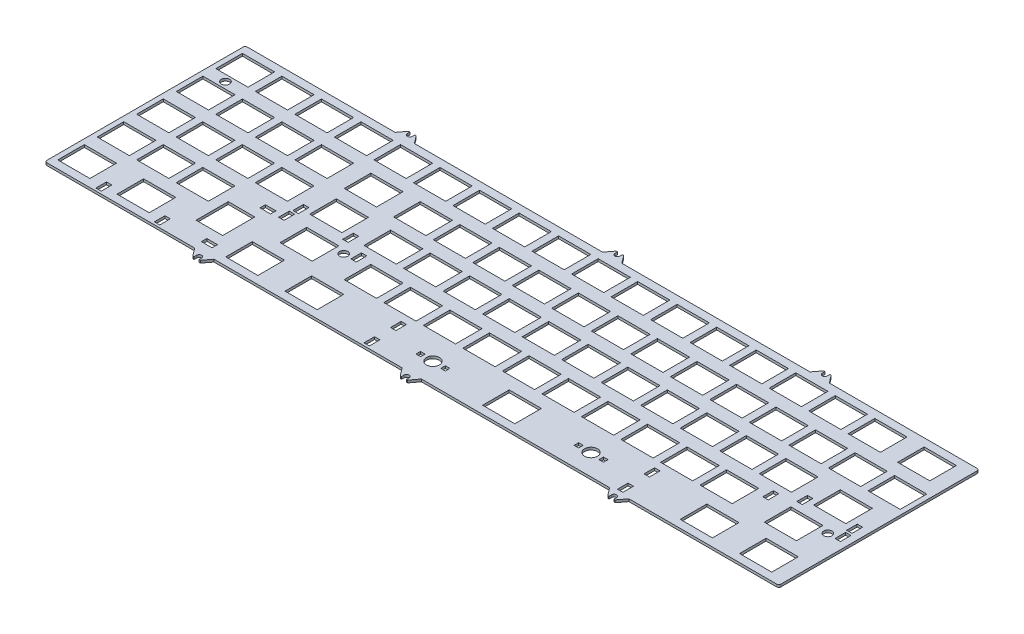
SolidWorks part; units mm, degrees
ref_plane "Front Plane" through (0, 0, 0) normal (0, 0, 1) x (1, 0, 0)
ref_plane "Top Plane" through (0, 0, 0) normal (0, 1, 0) x (1, 0, 0)
ref_plane "Right Plane" through (0, 0, 0) normal (1, 0, 0) x (0, 0, -1)
sketch "Sketch2" plane through (0, 0, 0) normal (0, 1, 0) x (1, 0, 0)
  line L0 (137.0625, 39.4) -> (121.4625, 39.4)
  line L1 (121.4625, 39.4) -> (121.4625, 26.6)
  line L2 (121.4625, 26.6) -> (137.0625, 26.6)
  line L3 (137.0625, 26.6) -> (137.0625, 39.4)
  line L4 (127.5375, 58.45) -> (111.9375, 58.45)
  line L5 (111.9375, 58.45) -> (111.9375, 45.65)
  line L6 (111.9375, 45.65) -> (127.5375, 45.65)
  line L7 (127.5375, 45.65) -> (127.5375, 58.45)
  line L8 (122.775, 77.5) -> (107.175, 77.5)
  line L9 (107.175, 77.5) -> (107.175, 64.7)
  line L10 (107.175, 64.7) -> (122.775, 64.7)
  line L11 (122.775, 64.7) -> (122.775, 77.5)
  line L12 (325.7312, 43.1) -> (325.7312, 48.2)
  line L13 (325.7312, 48.2) -> (323.1312, 48.2)
  line L14 (323.1312, 48.2) -> (323.1312, 43.1)
  line L15 (323.1312, 43.1) -> (325.7312, 43.1)
  line L16 (347.1312, 43.1) -> (347.1312, 48.2)
  line L17 (347.1312, 48.2) -> (349.7312, 48.2)
  line L18 (349.7312, 48.2) -> (349.7312, 43.1)
  line L19 (349.7312, 43.1) -> (347.1312, 43.1)
  line L20 (104.2437, 43.1) -> (104.2437, 48.2)
  line L21 (104.2437, 48.2) -> (106.8437, 48.2)
  line L22 (106.8437, 48.2) -> (106.8437, 43.1)
  line L23 (106.8437, 43.1) -> (104.2437, 43.1)
  line L24 (315.5687, 36.85) -> (315.5687, 41.95)
  line L25 (315.5687, 41.95) -> (312.9687, 41.95)
  line L26 (312.9687, 41.95) -> (312.9687, 36.85)
  line L27 (312.9687, 36.85) -> (315.5687, 36.85)
  line L28 (347.7687, 36.85) -> (347.7687, 41.95)
  line L29 (347.7687, 41.95) -> (350.3687, 41.95)
  line L30 (350.3687, 41.95) -> (350.3687, 36.85)
  line L31 (350.3687, 36.85) -> (347.7687, 36.85)
  line L32 (114.4062, 36.85) -> (114.4062, 41.95)
  line L33 (114.4062, 41.95) -> (117.0062, 41.95)
  line L34 (117.0062, 41.95) -> (117.0062, 36.85)
  line L35 (117.0062, 36.85) -> (114.4062, 36.85)
  line L36 (155.1875, 5) -> (155.1875, 10.1)
  line L37 (155.1875, 10.1) -> (152.5875, 10.1)
  line L38 (152.5875, 10.1) -> (152.5875, 5)
  line L39 (152.5875, 5) -> (155.1875, 5)
  line L40 (183.9625, 15.05) -> (183.9625, 12.85)
  line L41 (183.9625, 12.85) -> (181.7625, 12.85)
  line L42 (181.7625, 12.85) -> (181.7625, 15.05)
  line L43 (181.7625, 15.05) -> (183.9625, 15.05)
  line L44 (169.8125, 12.85) -> (169.8125, 15.05)
  line L45 (169.8125, 15.05) -> (172.0125, 15.05)
  line L46 (172.0125, 15.05) -> (172.0125, 12.85)
  line L47 (172.0125, 12.85) -> (169.8125, 12.85)
  line L48 (246.0125, 15.05) -> (246.0125, 12.85)
  line L49 (246.0125, 12.85) -> (248.2125, 12.85)
  line L50 (248.2125, 12.85) -> (248.2125, 15.05)
  line L51 (248.2125, 15.05) -> (246.0125, 15.05)
  line L52 (260.1625, 12.85) -> (260.1625, 15.05)
  line L53 (260.1625, 15.05) -> (257.9625, 15.05)
  line L54 (257.9625, 15.05) -> (257.9625, 12.85)
  line L55 (257.9625, 12.85) -> (260.1625, 12.85)
  line L56 (82.8437, 43.1) -> (82.8437, 48.2)
  line L57 (82.8437, 48.2) -> (80.2437, 48.2)
  line L58 (80.2437, 48.2) -> (80.2437, 43.1)
  line L59 (80.2437, 43.1) -> (82.8437, 43.1)
  line L60 (82.2062, 36.85) -> (82.2062, 41.95)
  line L61 (82.2062, 41.95) -> (79.6062, 41.95)
  line L62 (79.6062, 41.95) -> (79.6062, 36.85)
  line L63 (79.6062, 36.85) -> (82.2062, 36.85)
  line L64 (25.975, 5) -> (25.975, 10.1)
  line L65 (25.975, 10.1) -> (23.375, 10.1)
  line L66 (23.375, 10.1) -> (23.375, 5)
  line L67 (23.375, 5) -> (25.975, 5)
  line L68 (51.575, 5) -> (51.575, 10.1)
  line L69 (51.575, 10.1) -> (54.175, 10.1)
  line L70 (54.175, 10.1) -> (54.175, 5)
  line L71 (54.175, 5) -> (51.575, 5)
  line L72 (76.3, 10.675) -> (71.2, 10.675)
  line L73 (71.2, 10.675) -> (71.2, 8.075)
  line L74 (71.2, 8.075) -> (76.3, 8.075)
  line L75 (76.3, 8.075) -> (76.3, 10.675)
  line L76 (76.3, 36.275) -> (71.2, 36.275)
  line L77 (71.2, 36.275) -> (71.2, 38.875)
  line L78 (71.2, 38.875) -> (76.3, 38.875)
  line L79 (76.3, 38.875) -> (76.3, 36.275)
  line L80 (155.1875, 22.9) -> (155.1875, 17.8)
  line L81 (155.1875, 17.8) -> (152.5875, 17.8)
  line L82 (152.5875, 17.8) -> (152.5875, 22.9)
  line L83 (152.5875, 22.9) -> (155.1875, 22.9)
  line L84 (277.3875, 22.9) -> (277.3875, 17.8)
  line L85 (277.3875, 17.8) -> (274.7875, 17.8)
  line L86 (274.7875, 17.8) -> (274.7875, 22.9)
  line L87 (274.7875, 22.9) -> (277.3875, 22.9)
  line L88 (274.7875, 5) -> (274.7875, 10.1)
  line L89 (274.7875, 10.1) -> (277.3875, 10.1)
  line L90 (277.3875, 10.1) -> (277.3875, 5)
  line L91 (277.3875, 5) -> (274.7875, 5)
  line L92 (0, 4.75) -> (0, 99.35)
  line L93 (353.775, 4.75) -> (353.775, 99.35)
  line L94 (75.0875, 104.1) -> (72.2375, 100.35)
  line L95 (75.0875, 104.1) -> (75.6875, 104.1)
  line L96 (75.6875, 104.1) -> (75.6875, 103.6)
  line L97 (78.6875, 104.1) -> (81.5375, 100.35)
  line L98 (78.6875, 104.1) -> (78.0875, 104.1)
  line L99 (78.0875, 104.1) -> (78.0875, 103.6)
  line L100 (175.0875, 104.1) -> (172.2375, 100.35)
  line L101 (175.0875, 104.1) -> (175.6875, 104.1)
  line L102 (178.6875, 104.1) -> (181.5375, 100.35)
  line L103 (178.6875, 104.1) -> (178.0875, 104.1)
  line L104 (275.0875, 104.1) -> (272.2375, 100.35)
  line L105 (275.0875, 104.1) -> (275.6875, 104.1)
  line L106 (278.6875, 104.1) -> (281.5375, 100.35)
  line L107 (278.6875, 104.1) -> (278.0875, 104.1)
  line L108 (272.2375, 100.35) -> (181.5375, 100.35)
  line L109 (172.2375, 100.35) -> (81.5375, 100.35)
  line L110 (72.2375, 100.35) -> (1, 100.35)
  line L111 (352.775, 100.35) -> (281.5375, 100.35)
  line L112 (272.2375, 3.75) -> (181.5375, 3.75)
  line L113 (172.2375, 3.75) -> (81.5375, 3.75)
  line L114 (72.2375, 3.75) -> (1, 3.75)
  line L115 (352.775, 3.75) -> (281.5375, 3.75)
  line L116 (331.0625, 83.75) -> (346.5625, 83.75)
  line L117 (346.5625, 83.75) -> (346.5625, 96.55)
  line L118 (346.5625, 96.55) -> (331.0625, 96.55)
  line L119 (331.0625, 96.55) -> (331.0625, 83.75)
  line L120 (307.25, 83.75) -> (322.75, 83.75)
  line L121 (322.75, 83.75) -> (322.75, 96.55)
  line L122 (322.75, 96.55) -> (307.25, 96.55)
  line L123 (307.25, 96.55) -> (307.25, 83.75)
  line L124 (288.2, 83.75) -> (303.7, 83.75)
  line L125 (303.7, 83.75) -> (303.7, 96.55)
  line L126 (303.7, 96.55) -> (288.2, 96.55)
  line L127 (288.2, 96.55) -> (288.2, 83.75)
  line L128 (269.15, 83.75) -> (284.65, 83.75)
  line L129 (284.65, 83.75) -> (284.65, 96.55)
  line L130 (284.65, 96.55) -> (269.15, 96.55)
  line L131 (269.15, 96.55) -> (269.15, 83.75)
  line L132 (250.1, 83.75) -> (265.6, 83.75)
  line L133 (265.6, 83.75) -> (265.6, 96.55)
  line L134 (265.6, 96.55) -> (250.1, 96.55)
  line L135 (250.1, 96.55) -> (250.1, 83.75)
  line L136 (231.05, 83.75) -> (246.55, 83.75)
  line L137 (246.55, 83.75) -> (246.55, 96.55)
  line L138 (246.55, 96.55) -> (231.05, 96.55)
  line L139 (231.05, 96.55) -> (231.05, 83.75)
  line L140 (212, 83.75) -> (227.5, 83.75)
  line L141 (227.5, 83.75) -> (227.5, 96.55)
  line L142 (227.5, 96.55) -> (212, 96.55)
  line L143 (212, 96.55) -> (212, 83.75)
  line L144 (192.95, 83.75) -> (208.45, 83.75)
  line L145 (208.45, 83.75) -> (208.45, 96.55)
  line L146 (208.45, 96.55) -> (192.95, 96.55)
  line L147 (192.95, 96.55) -> (192.95, 83.75)
  line L148 (173.9, 83.75) -> (189.4, 83.75)
  line L149 (189.4, 83.75) -> (189.4, 96.55)
  line L150 (189.4, 96.55) -> (173.9, 96.55)
  line L151 (173.9, 96.55) -> (173.9, 83.75)
  line L152 (154.85, 83.75) -> (170.35, 83.75)
  line L153 (170.35, 83.75) -> (170.35, 96.55)
  line L154 (170.35, 96.55) -> (154.85, 96.55)
  line L155 (154.85, 96.55) -> (154.85, 83.75)
  line L156 (135.8, 83.75) -> (151.3, 83.75)
  line L157 (151.3, 83.75) -> (151.3, 96.55)
  line L158 (151.3, 96.55) -> (135.8, 96.55)
  line L159 (135.8, 96.55) -> (135.8, 83.75)
  line L160 (116.75, 83.75) -> (132.25, 83.75)
  line L161 (132.25, 83.75) -> (132.25, 96.55)
  line L162 (132.25, 96.55) -> (116.75, 96.55)
  line L163 (116.75, 96.55) -> (116.75, 83.75)
  line L164 (97.7, 83.75) -> (113.2, 83.75)
  line L165 (113.2, 83.75) -> (113.2, 96.55)
  line L166 (113.2, 96.55) -> (97.7, 96.55)
  line L167 (97.7, 96.55) -> (97.7, 83.75)
  line L168 (78.65, 83.75) -> (94.15, 83.75)
  line L169 (94.15, 83.75) -> (94.15, 96.55)
  line L170 (94.15, 96.55) -> (78.65, 96.55)
  line L171 (78.65, 96.55) -> (78.65, 83.75)
  line L172 (59.6, 77.5) -> (75.1, 77.5)
  line L173 (75.1, 64.7) -> (75.1, 77.5)
  line L174 (75.1, 96.55) -> (59.6, 96.55)
  line L175 (59.6, 77.5) -> (59.6, 64.7)
  line L176 (40.55, 77.5) -> (56.05, 77.5)
  line L177 (56.05, 64.7) -> (56.05, 77.5)
  line L178 (56.05, 96.55) -> (40.55, 96.55)
  line L179 (40.55, 77.5) -> (40.55, 64.7)
  line L180 (21.5, 77.5) -> (37, 77.5)
  line L181 (37, 64.7) -> (37, 77.5)
  line L182 (37, 96.55) -> (21.5, 96.55)
  line L183 (21.5, 77.5) -> (21.5, 64.7)
  line L184 (2.45, 77.5) -> (17.95, 77.5)
  line L185 (17.95, 64.7) -> (17.95, 77.5)
  line L186 (17.95, 96.55) -> (2.45, 96.55)
  line L187 (2.45, 77.5) -> (2.45, 64.7)
  line L188 (59.6, 64.7) -> (75.1, 64.7)
  line L189 (75.1, 83.75) -> (75.1, 96.55)
  line L190 (75.1, 83.75) -> (59.6, 83.75)
  line L191 (59.6, 96.55) -> (59.6, 83.75)
  line L192 (40.55, 64.7) -> (56.05, 64.7)
  line L193 (56.05, 83.75) -> (56.05, 96.55)
  line L194 (56.05, 83.75) -> (40.55, 83.75)
  line L195 (40.55, 96.55) -> (40.55, 83.75)
  line L196 (21.5, 64.7) -> (37, 64.7)
  line L197 (37, 83.75) -> (37, 96.55)
  line L198 (37, 83.75) -> (21.5, 83.75)
  line L199 (21.5, 96.55) -> (21.5, 83.75)
  line L200 (2.45, 64.7) -> (17.95, 64.7)
  line L201 (17.95, 83.75) -> (17.95, 96.55)
  line L202 (17.95, 83.75) -> (2.45, 83.75)
  line L203 (2.45, 96.55) -> (2.45, 83.75)
  line L204 (59.55, 45.65) -> (75.05, 45.65)
  line L205 (75.05, 45.65) -> (75.05, 58.45)
  line L206 (75.05, 58.45) -> (59.55, 58.45)
  line L207 (59.55, 58.45) -> (59.55, 45.65)
  line L208 (40.5, 45.65) -> (56, 45.65)
  line L209 (56, 45.65) -> (56, 58.45)
  line L210 (56, 58.45) -> (40.5, 58.45)
  line L211 (40.5, 58.45) -> (40.5, 45.65)
  line L212 (21.45, 45.65) -> (36.95, 45.65)
  line L213 (36.95, 45.65) -> (36.95, 58.45)
  line L214 (36.95, 58.45) -> (21.45, 58.45)
  line L215 (21.45, 58.45) -> (21.45, 45.65)
  line L216 (2.4, 45.65) -> (17.9, 45.65)
  line L217 (17.9, 45.65) -> (17.9, 58.45)
  line L218 (17.9, 58.45) -> (2.4, 58.45)
  line L219 (2.4, 58.45) -> (2.4, 45.65)
  line L220 (40.5, 26.6) -> (56, 26.6)
  line L221 (56, 26.6) -> (56, 39.4)
  line L222 (56, 39.4) -> (40.5, 39.4)
  line L223 (40.5, 39.4) -> (40.5, 26.6)
  line L224 (21.45, 26.6) -> (36.95, 26.6)
  line L225 (36.95, 26.6) -> (36.95, 39.4)
  line L226 (36.95, 39.4) -> (21.45, 39.4)
  line L227 (21.45, 39.4) -> (21.45, 26.6)
  line L228 (2.4, 26.6) -> (17.9, 26.6)
  line L229 (17.9, 26.6) -> (17.9, 39.4)
  line L230 (17.9, 39.4) -> (2.4, 39.4)
  line L231 (2.4, 39.4) -> (2.4, 26.6)
  line L232 (2.45, 7.55) -> (17.95, 7.55)
  line L233 (17.95, 7.55) -> (17.95, 20.35)
  line L234 (17.95, 20.35) -> (2.45, 20.35)
  line L235 (2.45, 20.35) -> (2.45, 7.55)
  line L236 (31.025, 7.55) -> (46.525, 7.55)
  line L237 (46.525, 7.55) -> (46.525, 20.35)
  line L238 (46.525, 20.35) -> (31.025, 20.35)
  line L239 (31.025, 20.35) -> (31.025, 7.55)
  line L240 (83.4125, 7.55) -> (98.9125, 7.55)
  line L241 (98.9125, 7.55) -> (98.9125, 20.35)
  line L242 (98.9125, 20.35) -> (83.4125, 20.35)
  line L243 (83.4125, 20.35) -> (83.4125, 7.55)
  line L244 (111.9875, 7.55) -> (127.4875, 7.55)
  line L245 (127.4875, 7.55) -> (127.4875, 20.35)
  line L246 (127.4875, 20.35) -> (111.9875, 20.35)
  line L247 (111.9875, 20.35) -> (111.9875, 7.55)
  line L248 (90.5562, 26.6) -> (106.0562, 26.6)
  line L249 (106.0562, 26.6) -> (106.0562, 39.4)
  line L250 (106.0562, 39.4) -> (90.5562, 39.4)
  line L251 (90.5562, 39.4) -> (90.5562, 26.6)
  line L252 (85.7937, 45.65) -> (101.2937, 45.65)
  line L253 (101.2937, 45.65) -> (101.2937, 58.45)
  line L254 (101.2937, 58.45) -> (85.7937, 58.45)
  line L255 (85.7937, 58.45) -> (85.7937, 45.65)
  line L256 (83.4125, 64.7) -> (98.9125, 64.7)
  line L257 (98.9125, 64.7) -> (98.9125, 77.5)
  line L258 (98.9125, 77.5) -> (83.4125, 77.5)
  line L259 (83.4125, 77.5) -> (83.4125, 64.7)
  line L260 (328.6812, 45.65) -> (344.1812, 45.65)
  line L261 (344.1812, 45.65) -> (344.1812, 58.45)
  line L262 (344.1812, 58.45) -> (328.6812, 58.45)
  line L263 (328.6812, 58.45) -> (328.6812, 45.65)
  line L264 (207.2375, 7.55) -> (222.7375, 7.55)
  line L265 (222.7375, 7.55) -> (222.7375, 20.35)
  line L266 (222.7375, 20.35) -> (207.2375, 20.35)
  line L267 (207.2375, 20.35) -> (207.2375, 7.55)
  line L268 (302.4875, 7.55) -> (317.9875, 7.55)
  line L269 (317.9875, 7.55) -> (317.9875, 20.35)
  line L270 (317.9875, 20.35) -> (302.4875, 20.35)
  line L271 (302.4875, 20.35) -> (302.4875, 7.55)
  line L272 (323.9187, 26.6) -> (339.4187, 26.6)
  line L273 (339.4187, 26.6) -> (339.4187, 39.4)
  line L274 (339.4187, 39.4) -> (323.9187, 39.4)
  line L275 (323.9187, 39.4) -> (323.9187, 26.6)
  line L276 (331.0625, 7.55) -> (346.5625, 7.55)
  line L277 (346.5625, 7.55) -> (346.5625, 20.35)
  line L278 (346.5625, 20.35) -> (331.0625, 20.35)
  line L279 (331.0625, 20.35) -> (331.0625, 7.55)
  line L280 (73.75, 15.725) -> (73.75, 31.225)
  line L281 (73.75, 31.225) -> (60.95, 31.225)
  line L282 (60.95, 31.225) -> (60.95, 15.725)
  line L283 (60.95, 15.725) -> (73.75, 15.725)
  line L284 (278.675, 64.7) -> (294.175, 64.7)
  line L285 (294.175, 64.7) -> (294.175, 77.5)
  line L286 (294.175, 77.5) -> (278.675, 77.5)
  line L287 (278.675, 77.5) -> (278.675, 64.7)
  line L288 (259.625, 64.7) -> (275.125, 64.7)
  line L289 (275.125, 64.7) -> (275.125, 77.5)
  line L290 (275.125, 77.5) -> (259.625, 77.5)
  line L291 (259.625, 77.5) -> (259.625, 64.7)
  line L292 (240.575, 64.7) -> (256.075, 64.7)
  line L293 (256.075, 64.7) -> (256.075, 77.5)
  line L294 (256.075, 77.5) -> (240.575, 77.5)
  line L295 (240.575, 77.5) -> (240.575, 64.7)
  line L296 (221.525, 64.7) -> (237.025, 64.7)
  line L297 (237.025, 64.7) -> (237.025, 77.5)
  line L298 (237.025, 77.5) -> (221.525, 77.5)
  line L299 (221.525, 77.5) -> (221.525, 64.7)
  line L300 (202.475, 64.7) -> (217.975, 64.7)
  line L301 (217.975, 64.7) -> (217.975, 77.5)
  line L302 (217.975, 77.5) -> (202.475, 77.5)
  line L303 (202.475, 77.5) -> (202.475, 64.7)
  line L304 (183.425, 64.7) -> (198.925, 64.7)
  line L305 (198.925, 64.7) -> (198.925, 77.5)
  line L306 (198.925, 77.5) -> (183.425, 77.5)
  line L307 (183.425, 77.5) -> (183.425, 64.7)
  line L308 (164.375, 64.7) -> (179.875, 64.7)
  line L309 (179.875, 64.7) -> (179.875, 77.5)
  line L310 (179.875, 77.5) -> (164.375, 77.5)
  line L311 (164.375, 77.5) -> (164.375, 64.7)
  line L312 (145.325, 64.7) -> (160.825, 64.7)
  line L313 (160.825, 64.7) -> (160.825, 77.5)
  line L314 (160.825, 77.5) -> (145.325, 77.5)
  line L315 (145.325, 77.5) -> (145.325, 64.7)
  line L316 (126.275, 64.7) -> (141.775, 64.7)
  line L317 (141.775, 64.7) -> (141.775, 77.5)
  line L318 (141.775, 77.5) -> (126.275, 77.5)
  line L319 (126.275, 77.5) -> (126.275, 64.7)
  line L320 (283.4375, 45.65) -> (298.9375, 45.65)
  line L321 (298.9375, 45.65) -> (298.9375, 58.45)
  line L322 (298.9375, 58.45) -> (283.4375, 58.45)
  line L323 (283.4375, 58.45) -> (283.4375, 45.65)
  line L324 (264.3875, 45.65) -> (279.8875, 45.65)
  line L325 (279.8875, 45.65) -> (279.8875, 58.45)
  line L326 (279.8875, 58.45) -> (264.3875, 58.45)
  line L327 (264.3875, 58.45) -> (264.3875, 45.65)
  line L328 (245.3375, 45.65) -> (260.8375, 45.65)
  line L329 (260.8375, 45.65) -> (260.8375, 58.45)
  line L330 (260.8375, 58.45) -> (245.3375, 58.45)
  line L331 (245.3375, 58.45) -> (245.3375, 45.65)
  line L332 (226.2875, 45.65) -> (241.7875, 45.65)
  line L333 (241.7875, 45.65) -> (241.7875, 58.45)
  line L334 (241.7875, 58.45) -> (226.2875, 58.45)
  line L335 (226.2875, 58.45) -> (226.2875, 45.65)
  line L336 (207.2375, 45.65) -> (222.7375, 45.65)
  line L337 (222.7375, 45.65) -> (222.7375, 58.45)
  line L338 (222.7375, 58.45) -> (207.2375, 58.45)
  line L339 (207.2375, 58.45) -> (207.2375, 45.65)
  line L340 (188.1875, 45.65) -> (203.6875, 45.65)
  line L341 (203.6875, 45.65) -> (203.6875, 58.45)
  line L342 (203.6875, 58.45) -> (188.1875, 58.45)
  line L343 (188.1875, 58.45) -> (188.1875, 45.65)
  line L344 (169.1375, 45.65) -> (184.6375, 45.65)
  line L345 (184.6375, 45.65) -> (184.6375, 58.45)
  line L346 (184.6375, 58.45) -> (169.1375, 58.45)
  line L347 (169.1375, 58.45) -> (169.1375, 45.65)
  line L348 (150.0875, 45.65) -> (165.5875, 45.65)
  line L349 (165.5875, 45.65) -> (165.5875, 58.45)
  line L350 (165.5875, 58.45) -> (150.0875, 58.45)
  line L351 (150.0875, 58.45) -> (150.0875, 45.65)
  line L352 (131.0375, 45.65) -> (146.5375, 45.65)
  line L353 (146.5375, 45.65) -> (146.5375, 58.45)
  line L354 (146.5375, 58.45) -> (131.0375, 58.45)
  line L355 (131.0375, 58.45) -> (131.0375, 45.65)
  line L356 (292.9625, 26.6) -> (308.4625, 26.6)
  line L357 (308.4625, 26.6) -> (308.4625, 39.4)
  line L358 (308.4625, 39.4) -> (292.9625, 39.4)
  line L359 (292.9625, 39.4) -> (292.9625, 26.6)
  line L360 (273.9125, 26.6) -> (289.4125, 26.6)
  line L361 (289.4125, 26.6) -> (289.4125, 39.4)
  line L362 (289.4125, 39.4) -> (273.9125, 39.4)
  line L363 (273.9125, 39.4) -> (273.9125, 26.6)
  line L364 (254.8625, 26.6) -> (270.3625, 26.6)
  line L365 (270.3625, 26.6) -> (270.3625, 39.4)
  line L366 (270.3625, 39.4) -> (254.8625, 39.4)
  line L367 (254.8625, 39.4) -> (254.8625, 26.6)
  line L368 (235.8125, 26.6) -> (251.3125, 26.6)
  line L369 (251.3125, 26.6) -> (251.3125, 39.4)
  line L370 (251.3125, 39.4) -> (235.8125, 39.4)
  line L371 (235.8125, 39.4) -> (235.8125, 26.6)
  line L372 (216.7625, 26.6) -> (232.2625, 26.6)
  line L373 (232.2625, 26.6) -> (232.2625, 39.4)
  line L374 (232.2625, 39.4) -> (216.7625, 39.4)
  line L375 (216.7625, 39.4) -> (216.7625, 26.6)
  line L376 (197.7125, 26.6) -> (213.2125, 26.6)
  line L377 (213.2125, 26.6) -> (213.2125, 39.4)
  line L378 (213.2125, 39.4) -> (197.7125, 39.4)
  line L379 (197.7125, 39.4) -> (197.7125, 26.6)
  line L380 (178.6625, 26.6) -> (194.1625, 26.6)
  line L381 (194.1625, 26.6) -> (194.1625, 39.4)
  line L382 (194.1625, 39.4) -> (178.6625, 39.4)
  line L383 (178.6625, 39.4) -> (178.6625, 26.6)
  line L384 (159.6125, 26.6) -> (175.1125, 26.6)
  line L385 (175.1125, 26.6) -> (175.1125, 39.4)
  line L386 (175.1125, 39.4) -> (159.6125, 39.4)
  line L387 (159.6125, 39.4) -> (159.6125, 26.6)
  line L388 (140.5625, 26.6) -> (156.0625, 26.6)
  line L389 (156.0625, 26.6) -> (156.0625, 39.4)
  line L390 (156.0625, 39.4) -> (140.5625, 39.4)
  line L391 (140.5625, 39.4) -> (140.5625, 26.6)
  line L392 (335.825, 64.7) -> (351.325, 64.7)
  line L393 (351.325, 64.7) -> (351.325, 77.5)
  line L394 (351.325, 77.5) -> (335.825, 77.5)
  line L395 (335.825, 77.5) -> (335.825, 64.7)
  line L396 (316.775, 64.7) -> (332.275, 64.7)
  line L397 (332.275, 64.7) -> (332.275, 77.5)
  line L398 (332.275, 77.5) -> (316.775, 77.5)
  line L399 (316.775, 77.5) -> (316.775, 64.7)
  line L400 (297.725, 64.7) -> (313.225, 64.7)
  line L401 (313.225, 64.7) -> (313.225, 77.5)
  line L402 (313.225, 77.5) -> (297.725, 77.5)
  line L403 (297.725, 77.5) -> (297.725, 64.7)
  line L404 (302.4875, 45.65) -> (317.9875, 45.65)
  line L405 (317.9875, 45.65) -> (317.9875, 58.45)
  line L406 (317.9875, 58.45) -> (302.4875, 58.45)
  line L407 (302.4875, 58.45) -> (302.4875, 45.65)
  line L408 (278.0875, 102.85) -> (278.0875, 104.1)
  line L409 (275.6875, 102.85) -> (275.6875, 104.1)
  line L410 (178.0875, 102.85) -> (178.0875, 104.1)
  line L411 (175.6875, 102.85) -> (175.6875, 104.1)
  line L412 (78.0875, 102.85) -> (78.0875, 103.6)
  line L413 (75.6875, 102.85) -> (75.6875, 103.6)
  line L414 (75.0875, 0) -> (72.2375, 3.75)
  line L415 (75.0875, 0) -> (75.6875, 0)
  line L416 (75.6875, 0) -> (75.6875, 0.5)
  line L417 (78.6875, 0) -> (81.5375, 3.75)
  line L418 (78.6875, 0) -> (78.0875, 0)
  line L419 (78.0875, 0) -> (78.0875, 0.5)
  line L420 (175.0875, 0) -> (172.2375, 3.75)
  line L421 (175.0875, 0) -> (175.6875, 0)
  line L422 (178.6875, 0) -> (181.5375, 3.75)
  line L423 (178.6875, 0) -> (178.0875, 0)
  line L424 (275.0875, 0) -> (272.2375, 3.75)
  line L425 (275.0875, 0) -> (275.6875, 0)
  line L426 (278.6875, 0) -> (281.5375, 3.75)
  line L427 (278.6875, 0) -> (278.0875, 0)
  line L428 (278.0875, 1.25) -> (278.0875, 0)
  line L429 (275.6875, 1.25) -> (275.6875, 0)
  line L430 (178.0875, 1.25) -> (178.0875, 0)
  line L431 (175.6875, 1.25) -> (175.6875, 0)
  line L432 (78.0875, 1.25) -> (78.0875, 0.5)
  line L433 (75.6875, 1.25) -> (75.6875, 0.5)
  circle A0 centre (176.8875, 13.95) radius 3.125
  circle A1 centre (253.0875, 13.95) radius 3.125
  arc A2 (0, 4.75) -> (1, 3.75) centre (1, 4.75) ccw
  arc A3 (1, 100.35) -> (0, 99.35) centre (1, 99.35) ccw
  arc A4 (75.6875, 102.85) -> (78.0875, 102.85) centre (76.8875, 102.85) ccw
  arc A5 (175.6875, 102.85) -> (178.0875, 102.85) centre (176.8875, 102.85) ccw
  arc A6 (275.6875, 102.85) -> (278.0875, 102.85) centre (276.8875, 102.85) ccw
  arc A7 (352.775, 3.75) -> (353.775, 4.75) centre (352.775, 4.75) ccw
  arc A8 (353.775, 99.35) -> (352.775, 100.35) centre (352.775, 99.35) ccw
  circle A9 centre (343.9187, 37.25) radius 2
  circle A10 centre (110.5562, 37.25) radius 2
  circle A11 centre (10.2, 80.625) radius 2
  arc A12 (78.0875, 1.25) -> (75.6875, 1.25) centre (76.8875, 1.25) ccw
  arc A13 (178.0875, 1.25) -> (175.6875, 1.25) centre (176.8875, 1.25) ccw
  arc A14 (278.0875, 1.25) -> (275.6875, 1.25) centre (276.8875, 1.25) ccw
extrude "Boss-Extrude1" add sketch "Sketch2" against normal blind 1.2
